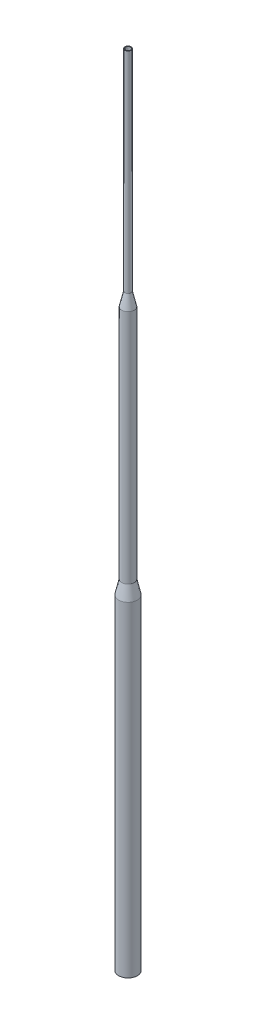
SolidWorks part; units mm, degrees
ref_plane "Plan de face" through (0, 0, 0) normal (0, 0, 1) x (1, 0, 0)
ref_plane "Plan de dessus" through (0, 0, 0) normal (0, 1, 0) x (1, 0, 0)
ref_plane "Plan de droite" through (0, 0, 0) normal (1, 0, 0) x (0, 0, -1)
sketch "Esquisse1" plane through (0, 0, 0) normal (0, 1, 0) x (1, 0, 0)
  circle A0 centre (0, 0) radius 5
  dimension "D1" = 10
extrude "Boss.-Extru.1" add sketch "Esquisse1" along normal blind 1280
sketch "Esquisse2" plane through (0, 0, 0) normal (0, 1, 0) x (1, 0, 0)
  circle A0 centre (0, 0) radius 15
  dimension "D1" = 30
extrude "Boss.-Extru.2" add sketch "Esquisse2" along normal blind 500
sketch "Esquisse3" plane through (0, 500, 0) normal (0, 1, 0) x (1, 0, 0)
  circle A0 centre (0, 0) radius 10
  dimension "D1" = 20
extrude "Boss.-Extru.3" add sketch "Esquisse3" along normal blind 400
chamfer "Chanfrein1" distance 10 angle 77 2 edges at (0, 500, 10) (0, 900, 5) first distance on face at (0, 500, 10) first distance on face at (0, 900, 5)
sketch "Esquisse4" plane through (0, 1280, 0) normal (0, 1, 0) x (1, 0, 0)
  circle A0 centre (0, 0) radius 4
  dimension "D1" = 8
extrude "Enlèv. mat.-Extru.1" cut sketch "Esquisse4" against normal through all both and the other way through all
